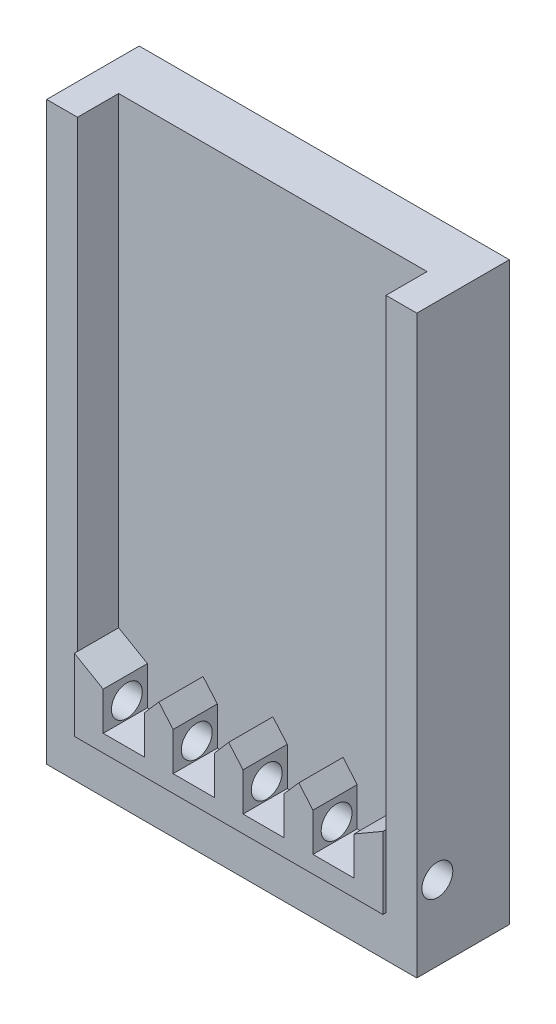
SolidWorks part; units mm, degrees
ref_plane "Plano frontal" through (0, 0, 0) normal (0, 0, 1) x (1, 0, 0)
ref_plane "Plano superior" through (0, 0, 0) normal (0, 1, 0) x (1, 0, 0)
ref_plane "Plano direito" through (0, 0, 0) normal (1, 0, 0) x (0, 0, -1)
sketch "Esboço1" plane through (0, 0, 0) normal (0, 0, 1) x (1, 0, 0)
  line L0 (1.5, 28) -> (1.5, 2)
  line L1 (0, 0) -> (18, 0)
  line L2 (0, 0) -> (0, 28)
  line L3 (0, 28) -> (18, 28)
  line L4 (18, 0) -> (18, 28)
  line L5 (1.5, 2) -> (16.5, 2)
  line L6 (16.5, 2) -> (16.5, 28)
  dimension "D1" = 28
  dimension "D2" = 18
  dimension "D3" = 26
  dimension "D4" = 15
  dimension "D5" = 1.5
extrude "Ressalto-extrusão1" add sketch "Esboço1" along normal blind 2.5 contours L5 L6 L3 L0 region at (9, 15, 0)
extrude "Ressalto-extrusão2" add sketch "Esboço1<3>" along normal blind 4.5 contours L6 L5 L0 L3 L2 L1 L4 region at (1.1671, 15, 0)
sketch "Esboço1<3>" plane through (0, 0, 0) normal (0, 0, 1) x (1, 0, 0) same geometry as "Esboço1"
sketch "Esboço2" plane through (0, 0, 2.5) normal (0, 0, 1) x (1, 0, 0)
  line L0 (1.5, 2) -> (1.5, 5.5)
  line L1 (1.5, 28) -> (1.5, 2) construction
  line L2 (1.5, 5.5) -> (2.9, 4.6917)
  line L3 (2.9, 4.6917) -> (2.9, 2.8296)
  line L4 (2.9, 2.8296) -> (4.9, 2.8296)
  line L5 (4.9, 2.8296) -> (4.9, 4.6917)
  line L6 (4.9, 4.6917) -> (5.6057, 5.5)
  line L7 (5.6057, 5.5) -> (6.3, 4.6917)
  line L8 (6.3, 4.6917) -> (6.3, 2.8296)
  line L9 (6.3, 2.8296) -> (8.3, 2.8296)
  line L10 (8.3, 2.8296) -> (8.3, 4.6917)
  line L11 (8.3, 4.6917) -> (9, 5.5)
  line L12 (9, 5.5) -> (9.7, 4.6917)
  line L13 (9.7, 4.6917) -> (9.7, 2.8296)
  line L14 (9.7, 2.8296) -> (11.7, 2.8296)
  line L15 (11.7, 2.8296) -> (11.7, 4.6917)
  line L16 (11.7, 4.6917) -> (12.4125, 5.5)
  line L17 (12.4125, 5.5) -> (13.1, 4.6917)
  line L18 (13.1, 4.6917) -> (13.1, 2.8296)
  line L19 (13.1, 2.8296) -> (15.1, 2.8296)
  line L20 (15.1, 2.8296) -> (15.1, 4.6917)
  line L21 (15.1, 4.6917) -> (16.5, 5.5)
  line L22 (16.5, 2) -> (16.5, 28) construction
  line L23 (16.5, 5.5) -> (16.5, 2)
  line L24 (16.5, 2) -> (1.5, 2)
  line L25 (1.5, 5.5) -> (16.5, 5.5) construction
  dimension "D2" = 30
  dimension "D3" = 3.5
  dimension "D4" = 1.4
  dimension "D5" = 1.4
  dimension "D6" = 1.4
  dimension "D7" = 1.4
  dimension "D8" = 1.4
  dimension "D9" = 2
  dimension "D10" = 2
  dimension "D11" = 2
  dimension "D12" = 30
  dimension "D13" = 0.8296
  dimension "D14" = 0.8296
  dimension "D15" = 0.8296
extrude "Ressalto-extrusão3" add sketch "Esboço2" along normal blind 2.15
sketch "Esboço3" plane through (18, 0, 0) normal (1, 0, 0) x (0, 0, -1)
  line L3 (-4.5, 0) -> (-4.5, 28) construction
  circle A0 centre (-3.5, 3.6333) radius 0.75
  dimension "D1" = 1.5
  dimension "D2" = 1
extrude "Corte-extrusão1" cut sketch "Esboço3" against normal through all
